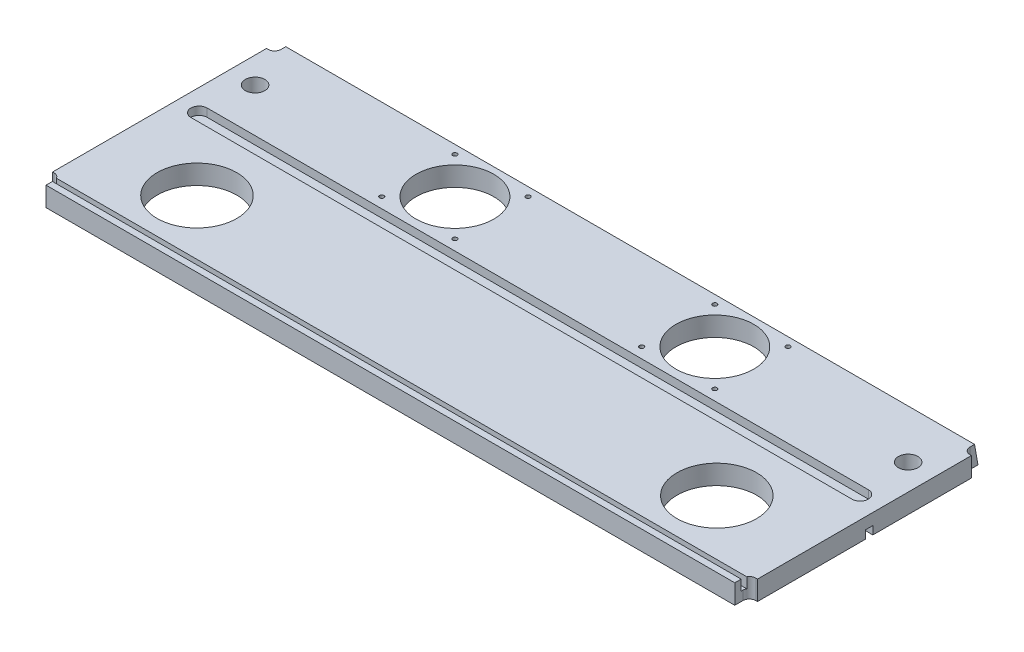
SolidWorks part; units mm, degrees
ref_plane "Front Plane" through (0, 0, 0) normal (0, 0, 1) x (1, 0, 0)
ref_plane "Top Plane" through (0, 0, 0) normal (0, 1, 0) x (1, 0, 0)
ref_plane "Right Plane" through (0, 0, 0) normal (1, 0, 0) x (0, 0, -1)
sketch "Sketch1" plane through (0, 0, 0) normal (0, 1, 0) x (1, 0, 0)
  line L0 (0, 0) -> (0, 118.8466) construction
  line L1 (336.55, 118.8466) -> (-336.55, 118.8466)
  line L2 (336.55, 118.8466) -> (336.55, -118.8466)
  line L3 (336.55, -118.8466) -> (-336.55, -118.8466)
  line L4 (-336.55, 118.8466) -> (-336.55, -118.8466)
  line L5 (336.55, 118.8466) -> (-336.55, -118.8466) construction
  line L6 (336.55, -118.8466) -> (-336.55, 118.8466) construction
  circle A0 centre (-254, -53.8734) radius 38.8937
  circle A1 centre (254, -53.8734) radius 38.8937
  point P0 (0, 0)
  dimension "D3" = 172.72
  dimension "D4" = 508
  dimension "D5" = 77.7875
  dimension "D1" = 673.1
  dimension "D2" = 237.6932
extrude "Boss-Extrude1" add sketch "Sketch1" along normal mid plane 19.05
sketch "Sketch2" plane through (0, 9.525, 0) normal (0, 1, 0) x (1, 0, 0)
  line L0 (-336.55, 118.8466) -> (-336.55, -118.8466) construction
  line L1 (-336.55, -107.89) -> (336.55, -107.89)
  line L2 (-336.55, -107.89) -> (-336.55, -112.589)
  line L3 (-336.55, -112.589) -> (336.55, -112.589)
  line L4 (336.55, -107.89) -> (336.55, -112.589)
  line L5 (336.55, -118.8466) -> (336.55, 118.8466) construction
  line L6 (-336.55, -118.8466) -> (336.55, -118.8466) construction
  dimension "D1" = 6.2576
  dimension "D2" = 4.699
extrude "Cut-Extrude1" cut sketch "Sketch2" against normal blind 10.16
sketch "Sketch3" plane through (0, 9.525, 0) normal (0, 1, 0) x (1, 0, 0)
  line L0 (-336.55, 118.8466) -> (-336.55, -107.89) construction
  line L1 (-336.55, 104.5591) -> (-344.4875, 104.5591)
  line L2 (-336.55, 104.5591) -> (-336.55, -104.5591)
  line L3 (-336.55, -104.5591) -> (-344.4875, -104.5591)
  line L4 (-344.4875, 104.5591) -> (-344.4875, -104.5591)
  line L5 (336.55, 118.8466) -> (-336.55, 118.8466) construction
  line L10 (336.55, -107.89) -> (336.55, 118.8466) construction
  line L11 (336.55, 104.5591) -> (344.4875, 104.5591)
  line L12 (336.55, 104.5591) -> (336.55, -104.5591)
  line L13 (336.55, -104.5591) -> (344.4875, -104.5591)
  line L14 (344.4875, 104.5591) -> (344.4875, -104.5591)
  line L15 (0, 0) -> (0, 51.9444) construction
  line L16 (0, 0) -> (-77.3937, 0) construction
  dimension "D1" = 14.2875
  dimension "D2" = 688.975
  dimension "D3" = 7.9375
extrude "Boss-Extrude2" add sketch "Sketch3" against normal up to surface (19.05 mm away) up to face at (-254, -9.525, 92.7672)
fillet "Fillet1" radius 6.35 4 edges at (336.55, 0, -104.5591) (336.55, 0, 104.5591) (-336.55, 0, -104.5591) (-336.55, 0, 104.5591)
sketch "Sketch4" plane through (336.55, 0, 0) normal (1, 0, 0) x (0, 0, -1)
  line L0 (118.8466, -9.525) -> (115.4876, 9.525)
  line L1 (110.9091, 9.525) -> (118.8466, 9.525) construction
  line L2 (115.4876, 9.525) -> (118.8466, 9.525)
  line L3 (118.8466, 9.525) -> (118.8466, -9.525)
  dimension "D1" = 10
extrude "Cut-Extrude2" cut sketch "Sketch4" against normal through all both and the other way through all
sketch "Sketch5" plane through (0, -9.525, 0) normal (0, -1, 0) x (1, 0, 0)
  line L0 (-323.0562, -17.2022) -> (323.0562, -17.2022) construction
  line L3 (-323.0562, -9.2012) -> (323.0562, -9.2012)
  line L4 (-323.0562, -25.2032) -> (323.0562, -25.2032)
  line L5 (-336.55, 118.8466) -> (336.55, 118.8466) construction
  line L6 (0, 0) -> (0, -17.2022) construction
  arc A0 (-323.0562, -9.2012) -> (-323.0562, -25.2032) centre (-323.0562, -17.2022) ccw
  arc A1 (323.0562, -25.2032) -> (323.0562, -9.2012) centre (323.0562, -17.2022) ccw
  point P6 (0, -17.2022)
  dimension "D1" = 16.002
  dimension "D2" = 136.0488
  dimension "D3" = 646.1125
extrude "Cut-Extrude3" cut sketch "Sketch5" along normal blind 7.9375 from surface starting at face at (0, 9.525, 115.7178)
sketch "Sketch6" plane through (0, 9.525, 0) normal (0, 1, 0) x (1, 0, 0)
  line L0 (0, 0) -> (0, 115.4876) construction
  line L2 (-344.4875, 104.5591) -> (-344.4875, -104.5591) construction
  line L4 (-323.0562, 25.2032) -> (323.0562, 25.2032) construction
  circle A0 centre (-319.0875, 68.0466) radius 9.525
  circle A1 centre (319.0875, 68.0466) radius 9.525
  circle A4 centre (127, 71.2216) radius 38
  circle A5 centre (-127, 71.2216) radius 38
  circle A6 centre (162.75, 106.9716) radius 2.159
  circle A7 centre (162.75, 35.4716) radius 2.159
  circle A8 centre (91.25, 35.4716) radius 2.159
  circle A9 centre (91.25, 106.9716) radius 2.159
  circle A10 centre (127, 71.2216) radius 50.5581 construction
  circle A11 centre (-127, 71.2216) radius 50.5581 construction
  circle A12 centre (-91.25, 106.9716) radius 2.159
  circle A13 centre (-91.25, 35.4716) radius 2.159
  circle A14 centre (-162.75, 35.4716) radius 2.159
  circle A15 centre (-162.75, 106.9716) radius 2.159
  dimension "D1" = 19.05
  dimension "D2" = 25.4
  dimension "D5" = 254
  dimension "D3" = 76
  dimension "D9" = 4.318
  dimension "D4" = 46.0184
  dimension "D6" = 42.8434
  dimension "D7" = 71.5
  dimension "D8" = 71.5
extrude "Cut-Extrude4" cut sketch "Sketch6" against normal through all both and the other way through all
sketch "Sketch8" plane through (0, 0, 0) normal (1, 0, 0) x (0, 0, -1)
  line L0 (1.1534, -9.525) -> (1.1534, -1.5875)
  line L1 (1.1534, -1.5875) -> (8.1534, -1.5875)
  line L2 (8.1534, -1.5875) -> (8.1534, -9.525)
  line L3 (-104.5591, -9.525) -> (104.5591, -9.525) construction
  line L4 (1.1534, -9.525) -> (8.1534, -9.525)
  line L5 (8.1534, -9.525) -> (8.1534, -12.8771) construction
  dimension "D1" = 7
  dimension "D2" = 7.9375
  dimension "D3" = 1.1534
extrude "Cut-Extrude5" cut sketch "Sketch8" against normal through all both and the other way through all
sketch "Sketch9" plane through (0, -9.525, 0) normal (0, -1, 0) x (1, 0, 0)
  circle A0 centre (254, 53.8734) radius 53.34
  dimension "D1" = 106.68
extrude "Boss-Extrude3" [suppressed] add sketch "Sketch9" along normal blind 2.54
